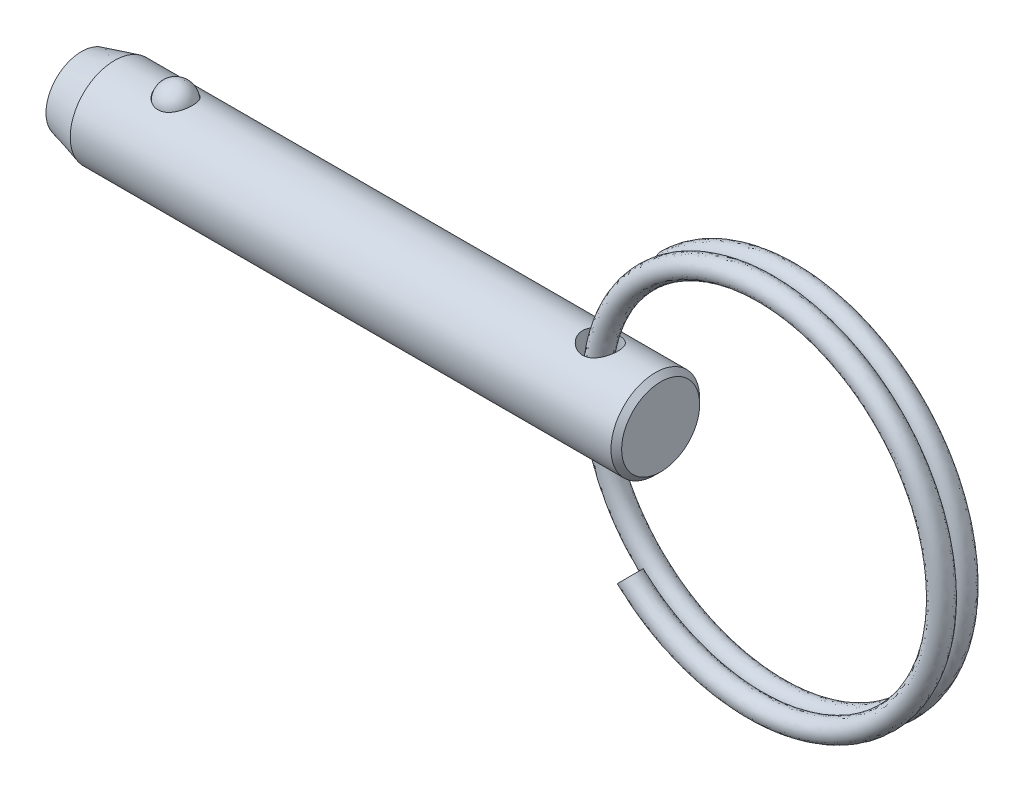
SolidWorks part; units mm, degrees
ref_plane "Front" through (0, 0, 0) normal (0, 0, 1) x (1, 0, 0)
ref_plane "Top" through (0, 0, 0) normal (0, 1, 0) x (1, 0, 0)
ref_plane "Right" through (0, 0, 0) normal (1, 0, 0) x (0, 0, -1)
sketch "Sketch1" plane through (0, 0, 0) normal (0, 0, 1) x (1, 0, 0)
  line L0 (20.7264, 2.794) -> (20.3454, 3.175)
  line L1 (20.3454, 3.175) -> (20.7264, 3.175) construction
  line L4 (20.7264, 2.794) -> (20.7264, 0)
  line L5 (20.7264, 3.175) -> (20.7264, 2.794) construction
  line L16 (20.3454, 3.175) -> (-18.3565, 3.175)
  line L17 (-20.7264, 3.175) -> (-20.7264, 2.54) construction
  line L19 (-18.3565, 3.175) -> (-20.7264, 3.175) construction
  line L22 (-20.7264, -3.175) -> (-18.3565, -3.175) construction
  line L23 (-13.9919, 2.8575) -> (-13.9919, -2.8575) construction
  line L24 (-20.7264, 0) -> (20.7264, 0)
  line L27 (20.7264, 0) -> (23.5204, 0) construction
  line L29 (-20.7264, 0) -> (-20.7264, -2.54) construction
  line L36 (15.1384, 0) -> (15.1384, 3.175) construction
  line L37 (-20.7264, 2.54) -> (-20.7264, 0)
  line L38 (-18.3565, -3.175) -> (20.7264, -3.175) construction
  line L39 (-20.7264, -2.54) -> (-20.7264, -3.175) construction
  line L40 (-18.3565, 3.175) -> (-20.7264, 2.54)
  line L42 (-18.3565, -3.175) -> (-20.7264, -2.54) construction
  line L43 (-18.3565, 3.175) -> (-18.3565, -3.175) construction
  circle A2 centre (-13.9919, 2.8575) radius 1.2319 construction
  point P35 (-12.8016, 3.175)
  dimension "A1" = 15
revolve "Revolve1" add sketch "Sketch1" angle 360 about L27
sketch "Sketch2" plane through (0, 0, 0) normal (0, 0, 1) x (1, 0, 0)
  line L0 (-12.7346, 2.8575) -> (-15.2492, 2.8575)
  line L1 (-13.9919, 4.0894) -> (-13.9919, 4.1148) construction
  line L2 (-12.7346, 2.8575) -> (-10.22, 2.8575) construction
  circle A0 centre (-13.9919, 2.8575) radius 1.2319 construction
  circle A1 centre (-13.9919, 2.8575) radius 1.2319 construction
  arc A2 (-15.2492, 2.8575) -> (-12.7346, 2.8575) centre (-13.9919, 2.8575) cw
  dimension "D1" = 0.0254
revolve "Cut-Revolve1" cut sketch "Sketch2" angle 360 about L2
sketch "Sketch3" plane through (0, 0, 0) normal (0, 0, 1) x (1, 0, 0)
  line L0 (-12.76, 2.8575) -> (-15.2238, 2.8575)
  line L1 (-12.76, 2.8575) -> (-10.2962, 2.8575) construction
  circle A0 centre (-13.9919, 2.8575) radius 1.2319 construction
  arc A1 (-12.76, 2.8575) -> (-15.2238, 2.8575) centre (-13.9919, 2.8575) ccw
revolve "Revolve2" add sketch "Sketch3" angle 360 about L1
sketch "Sketch4" plane through (0, 0, 0) normal (0, 0, 1) x (1, 0, 0)
  line L1 (16.4084, -3.175) -> (17.6784, -3.175)
  line L2 (16.4084, -3.175) -> (16.4084, 3.175)
  line L3 (16.4084, 3.175) -> (17.6784, 3.175)
  line L4 (17.6784, -3.175) -> (17.6784, 3.175)
  line L5 (16.4084, -3.175) -> (16.4084, -4.445) construction
  line L6 (17.6784, 3.175) -> (20.7264, 3.175) construction
  line L8 (15.1384, -3.175) -> (15.1384, 3.175) construction
  line L9 (15.1384, 0) -> (16.4084, 0) construction
  line L11 (16.4084, 0) -> (17.6784, 0) construction
  line L12 (20.3454, 3.175) -> (-18.3565, 3.175) construction
  line L14 (-18.3565, -3.175) -> (20.7264, -3.175) construction
  dimension "D1" = 2.54
revolve "Cut-Revolve2" cut sketch "Sketch4" angle 360 about L2
sketch "Sketch5" plane through (0, 0, 0) normal (0, 0, 1) x (1, 0, 0)
  line L0 (0, 0) -> (15.4314, 0) construction
  line L1 (15.4314, 0) -> (15.4314, 3.175) construction
  line L2 (20.3454, 3.175) -> (-18.3565, 3.175) construction
  line L3 (28.8934, 0) -> (42.3554, 0) construction
  line L4 (17.6784, 3.175) -> (17.3854, 3.175) construction
  line L5 (16.4084, 3.175) -> (17.6784, 3.175) construction
  line L6 (15.8112, 3.175) -> (15.8112, -3.175) construction
  line L7 (15.4314, 3.175) -> (15.1384, 3.175) construction
  line L8 (16.4084, -3.175) -> (17.6784, -3.175) construction
  line L9 (15.8112, -3.175) -> (17.6784, -3.175) construction
  line L10 (15.4314, 0) -> (28.8934, 0) construction
  line L12 (17.3854, 3.175) -> (15.8112, 3.175) construction
  line L13 (28.8934, 11.938) -> (28.8934, 13.462) construction
  circle A0 centre (28.8934, 0) radius 13.462
  circle A1 centre (28.8934, 0) radius 11.938 construction
  circle A2 centre (28.8934, 0) radius 12.7 construction
  point P26 (28.8934, 12.7)
curve "Helix/Spiral1" pitch 1.5494 height 1.3557 radius 13.462 left hand yes centre (28.8934, 0, 0) axis (0, 0, -1) start towards (1, 0, 0)
sketch "Sketch6" plane through (114.0038, 0, 0) normal (0, 1, 0) x (0, 0, -1)
  line L0 (0, 97.0484) -> (0, 97.8104) construction
  line L1 (0, 97.8104) -> (0, 98.5724) construction
  circle A0 centre (0, 97.8104) radius 0.762
  dimension "D1" = 1.524
sketch "Sketch7" plane through (0, 0, 0) normal (0, 0, 1) x (1, 0, 0)
  circle A0 centre (28.8934, 0) radius 13.462 construction
  circle A1 centre (28.8934, 0) radius 13.462
curve "Helix/Spiral2" pitch 1.5494 height 1.3557 radius 13.462 left hand yes centre (28.8934, 0, 0) axis (0, 0, 1) start towards (1, 0, 0)
sweep "Sweep1" add profiles "Sketch6" path "Helix/Spiral1"
sweep "Sweep2" add profiles "Sketch6<2>" path "Helix/Spiral2"
sketch "Sketch6<2>" plane through (114.0038, 0, 0) normal (0, 1, 0) x (0, 0, -1) same geometry as "Sketch6"
equation "\"D12@Sketch1\"=\"A@Sketch1\" * 0.80"
equation "\"D2@Sketch1\"=\"A@Sketch1\" * 0.9"
equation "\"D1@Sketch4\" = \"A@Sketch1\" / 2.5"
equation "\"Ring OD@Sketch5\" = \"R Ring Dia@Sketch5\" * 0.06"
equation "\"D4@Helix/Spiral1\"=\"Ring OD@Sketch5\" + 0.001"
equation "\"D1@Sketch6\"=\"Ring OD@Sketch5\""
equation "\"D4@Helix/Spiral2\" = \"D4@Helix/Spiral1\""
equation "\"D5@Helix/Spiral2\" = \"D5@Helix/Spiral1\""
